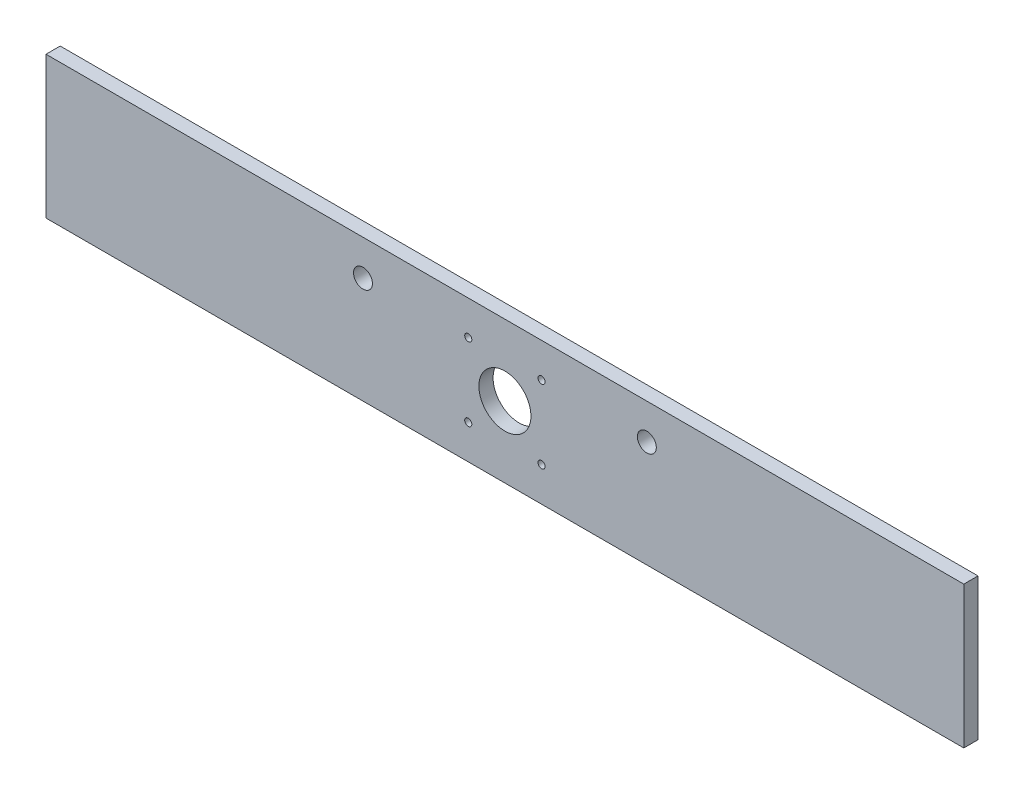
SolidWorks part; units mm, degrees
ref_plane "Front Plane" through (0, 0, 0) normal (0, 0, 1) x (1, 0, 0)
ref_plane "Top Plane" through (0, 0, 0) normal (0, 1, 0) x (1, 0, 0)
ref_plane "Right Plane" through (0, 0, 0) normal (1, 0, 0) x (0, 0, -1)
sketch "Sketch1" plane through (0, 0, 0) normal (0, 0, 1) x (1, 0, 0)
  line L0 (0, -1000) -> (0, 49000) construction
  line L1 (-194, -30) -> (194, -30)
  line L3 (-194, 30) -> (194, 30)
  line L7 (-1000, 0) -> (49000, 0) construction
  line L8 (194, 30) -> (194, -30)
  line L20 (-194, 30) -> (-194, -30)
  line L25 (-1145.7551, 15) -> (48854.2449, 15) construction
  circle A1 centre (60, 15) radius 4
  circle A2 centre (-60, 15) radius 4
  circle A11 centre (0, 0) radius 11
  point P0 (0, 0)
  dimension "D8" = 8
  dimension "D9" = 8
  dimension "D10" = 60
  dimension "D11" = 60
  dimension "D4" = 194
  dimension "D5" = 22
  dimension "D2" = 60
  dimension "D3" = 15
  dimension "D17" = 15
extrude "Boss-Extrude1" add sketch "Sketch1" along normal blind 6 contours L1 L8 L3 L20 A2 A1 region at (-190.0739, 0, 0)
sketch "Sketch2" plane through (0, 0, 6) normal (0, 0, 1) x (1, 0, 0)
  line L0 (-1000, 0) -> (49000, 0) construction
  line L1 (0, -1000) -> (0, 49000) construction
  circle A0 centre (15.495, 15.495) radius 1.5
  circle A4 centre (-15.495, 15.495) radius 1.5
  circle A5 centre (15.495, -15.495) radius 1.5
  circle A6 centre (-15.495, -15.495) radius 1.5
  dimension "D1" = 3
  dimension "D2" = 15.495
  dimension "D3" = 15.495
extrude "Cut-Extrude1" cut sketch "Sketch2" against normal up to next
